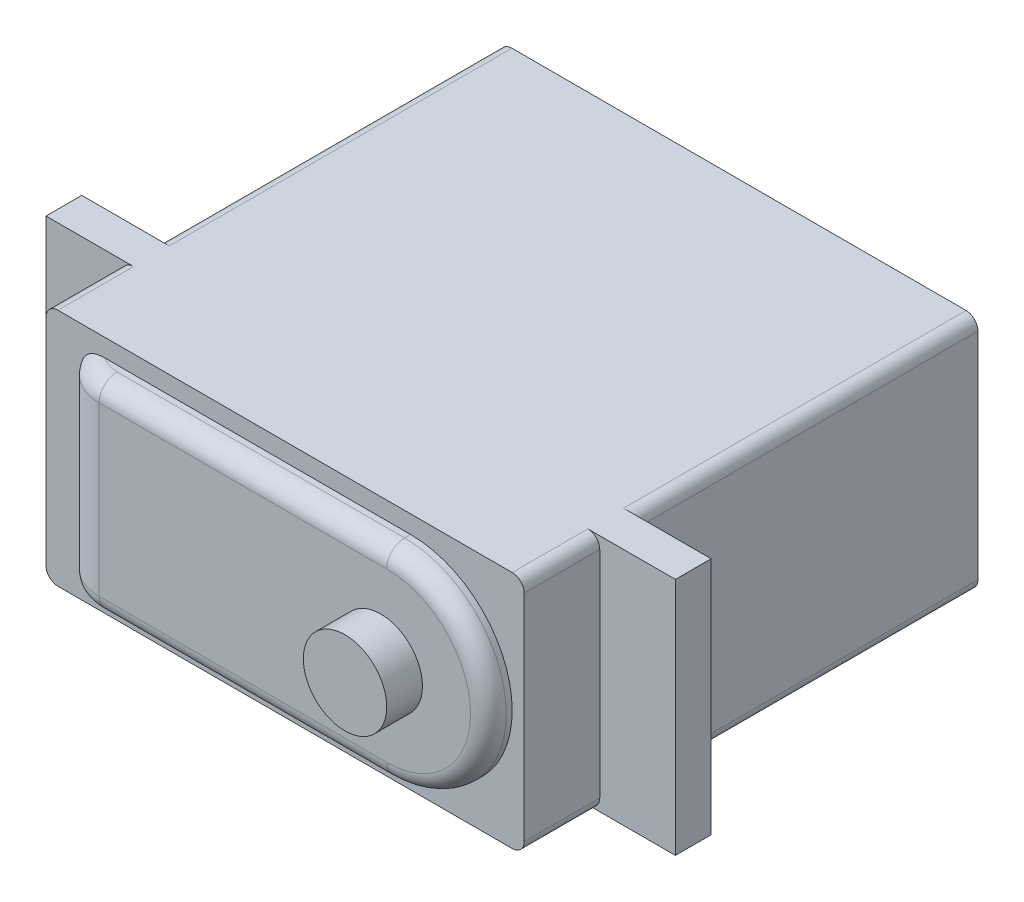
SolidWorks part; units mm, degrees
ref_plane "Front Plane" through (0, 0, 0) normal (0, 0, 1) x (1, 0, 0)
ref_plane "Top Plane" through (0, 0, 0) normal (0, 1, 0) x (1, 0, 0)
ref_plane "Right Plane" through (0, 0, 0) normal (1, 0, 0) x (0, 0, -1)
sketch "Sketch1" plane through (0, 0, 0) normal (0, 0, 1) x (1, 0, 0)
  line L1 (-20.066, 10.033) -> (20.066, 10.033)
  line L2 (-20.066, 10.033) -> (-20.066, -10.033)
  line L3 (-20.066, -10.033) -> (20.066, -10.033)
  line L4 (20.066, 10.033) -> (20.066, -10.033)
  line L5 (-20.066, 10.033) -> (20.066, -10.033) construction
  line L6 (-20.066, -10.033) -> (20.066, 10.033) construction
  point P0 (0, 0)
  dimension "D1" = 40.132
  dimension "D2" = 20.066
extrude "Boss-Extrude1" add sketch "Sketch1" along normal blind 38.1
ref_plane "Plane1" through (0, 0, 31.75) normal (0, 0, -1) x (-1, 0, 0)
sketch "Sketch2" plane through (0, 0, 31.75) normal (0, 0, -1) x (-1, 0, 0)
  line L0 (20.066, -10.033) -> (-20.066, -10.033) construction
  line L1 (20.066, 10.033) -> (26.416, 10.033)
  line L2 (0, 0) -> (0, 10.033) construction
  line L3 (20.066, -10.033) -> (26.416, -10.033)
  line L4 (26.416, 10.033) -> (26.416, -10.033)
  line L5 (26.416, 0) -> (20.066, 0) construction
  line L8 (20.066, 0) -> (20.066, 10.033)
  line L9 (-20.066, 10.033) -> (20.066, 10.033) construction
  line L11 (-25.146, 7.747) -> (-25.146, 10.033) construction
  line L12 (-26.416, 0) -> (-20.066, 0) construction
  line L13 (-20.066, 0) -> (-20.066, 10.033)
  line L14 (-26.416, 10.033) -> (-26.416, -10.033)
  line L15 (-20.066, -10.033) -> (-26.416, -10.033)
  line L16 (-20.066, 10.033) -> (-26.416, 10.033)
  line L17 (-20.066, -10.033) -> (-20.066, 10.033) construction
  line L18 (0, 10.033) -> (-20.066, 10.033) construction
  line L19 (0, 10.033) -> (0, -10.033) construction
  line L20 (0, -10.033) -> (-20.066, -10.033) construction
  line L21 (-20.066, 10.033) -> (-20.066, -10.033) construction
  line L22 (0, 10.033) -> (-20.066, -10.033) construction
  line L23 (0, -10.033) -> (-20.066, 10.033) construction
  line L24 (20.066, 10.033) -> (20.066, -10.033)
  line L25 (-20.066, 10.033) -> (-20.066, -10.033)
  circle A0 centre (25.146, 5.715) radius 2.032 construction
  circle A1 centre (25.146, -5.715) radius 2.032 construction
  circle A2 centre (-25.146, -5.715) radius 2.032 construction
  circle A3 centre (-25.146, 5.715) radius 2.032 construction
  circle A4 centre (-10.033, 0) radius 3.81 construction
  point P32 (-10.033, 0)
  dimension "D2" = 4.064
  dimension "D3" = 7.62
  dimension "D1" = 6.35
  dimension "D4" = 1.27
  dimension "D5" = 2.286
extrude "Boss-Extrude2" add sketch "Sketch2" along normal blind 3 contours L8 L24 L3 L4 L1 A0 A1 | L25 L13 L16 L14 L15 A2 A3 region at (-23.241, 0, 31.75) region at (23.241, 0, 31.75)
sketch "Sketch6" plane through (0, 0, 38.1) normal (0, 0, 1) x (1, 0, 0)
  line L0 (10.533, 0) -> (20.066, 0) construction
  line L1 (-17.066, 8.533) -> (10.533, 8.533)
  line L2 (-17.066, 8.533) -> (-17.066, -8.533)
  line L3 (-17.066, -8.533) -> (10.533, -8.533)
  line L4 (10.533, 8.533) -> (10.533, -8.533) construction
  line L5 (20.066, -10.033) -> (20.066, 10.033) construction
  line L6 (-20.066, 10.033) -> (-20.066, -10.033) construction
  line L7 (20.066, 10.033) -> (-20.066, 10.033) construction
  line L8 (19.066, 0) -> (20.066, 0) construction
  arc A0 (10.533, 8.533) -> (10.533, -8.533) centre (10.533, 0) ccw construction
  arc A1 (10.533, -8.533) -> (10.533, 8.533) centre (10.533, 0) ccw
  dimension "D1" = 3
  dimension "D2" = 1.5
  dimension "D3" = 1
extrude "Boss-Extrude4" add sketch "Sketch6" along normal blind 2
sketch "Sketch5" plane through (0, 0, 40.1) normal (0, 0, 1) x (1, 0, 0)
  circle A0 centre (10.033, 0) radius 3.81 construction
  circle A1 centre (10.033, 0) radius 3.81 construction
  circle A2 centre (10.033, 0) radius 3.5
  dimension "D1" = 7
extrude "Boss-Extrude3" add sketch "Sketch5" along normal blind 3
fillet "Fillet2" radius 4 1 edges at (-17.066, 0, 40.1)
fillet "Fillet3" radius 1.5 5 edges at (-15.6019, -8.533, 39.5641) (-15.6019, 8.533, 39.5641) (-1.5344, 8.533, 40.1) (19.066, 0, 40.1) (-1.5344, -8.533, 40.1)
fillet "Fillet4" radius 1 8 edges at (20.066, 10.033, 14.375) (20.066, 10.033, 34.925) (-20.066, 10.033, 14.375) (-20.066, 10.033, 34.925) (-20.066, -10.033, 14.375) (20.066, -10.033, 14.375) (20.066, -10.033, 34.925) (-20.066, -10.033, 34.925)
equation "\"flipWidth\"= 6.5"
equation "\"flipHeight\"= 4"
equation "\"spindleLength\"= 7.75"
equation "\"bearingID\"= 0.1559"
equation "\"motorWidth\"= 0.79"
equation "\"motorHeight\"= 1.0"
equation "\"motorLength\"= 1.58"
equation "\"spindleMaxDiam\"= 2.75"
equation "\"totalLength\"= 15"
equation "\"D1@Sketch1\"=\"motorLength\""
equation "\"D2@Sketch1\"=\"motorWidth\""
